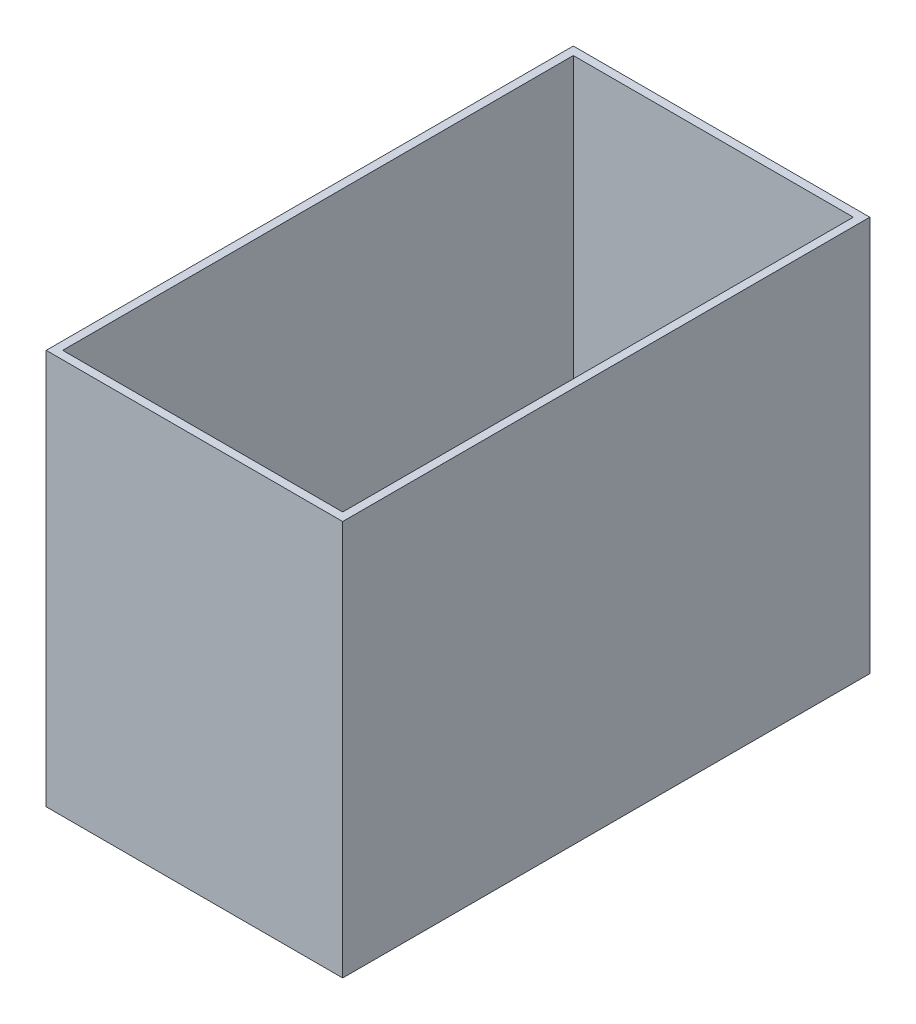
SolidWorks part; units mm, degrees
ref_plane "Front Plane" through (0, 0, 0) normal (0, 0, 1) x (1, 0, 0)
ref_plane "Top Plane" through (0, 0, 0) normal (0, 1, 0) x (1, 0, 0)
ref_plane "Right Plane" through (0, 0, 0) normal (1, 0, 0) x (0, 0, -1)
sketch "Sketch1" plane through (0, 0, 0) normal (0, 1, 0) x (1, 0, 0)
  line L1 (0, 0) -> (228.6, 0)
  line L2 (0, 0) -> (0, 406.4)
  line L3 (0, 406.4) -> (228.6, 406.4)
  line L4 (228.6, 0) -> (228.6, 406.4)
  dimension "D1" = 228.6
  dimension "D2" = 406.4
extrude "Boss-Extrude1" add sketch "Sketch1" along normal blind 304.8
sketch "Sketch2" plane through (0, 304.8, 0) normal (0, 1, 0) x (1, 0, 0)
  line L0 (228.6, 406.4) -> (0, 406.4) construction
  line L1 (6.35, 400.05) -> (222.25, 400.05)
  line L2 (6.35, 400.05) -> (6.35, 6.35)
  line L3 (6.35, 6.35) -> (222.25, 6.35)
  line L4 (222.25, 400.05) -> (222.25, 6.35)
  line L5 (0, 0) -> (228.6, 0) construction
  line L6 (228.6, 0) -> (228.6, 406.4) construction
  line L7 (0, 406.4) -> (0, 0) construction
  dimension "D1" = 6.35
  dimension "D2" = 6.35
  dimension "D3" = 6.35
  dimension "D4" = 6.35
extrude "Cut-Extrude1" cut sketch "Sketch2" against normal blind 298.45
